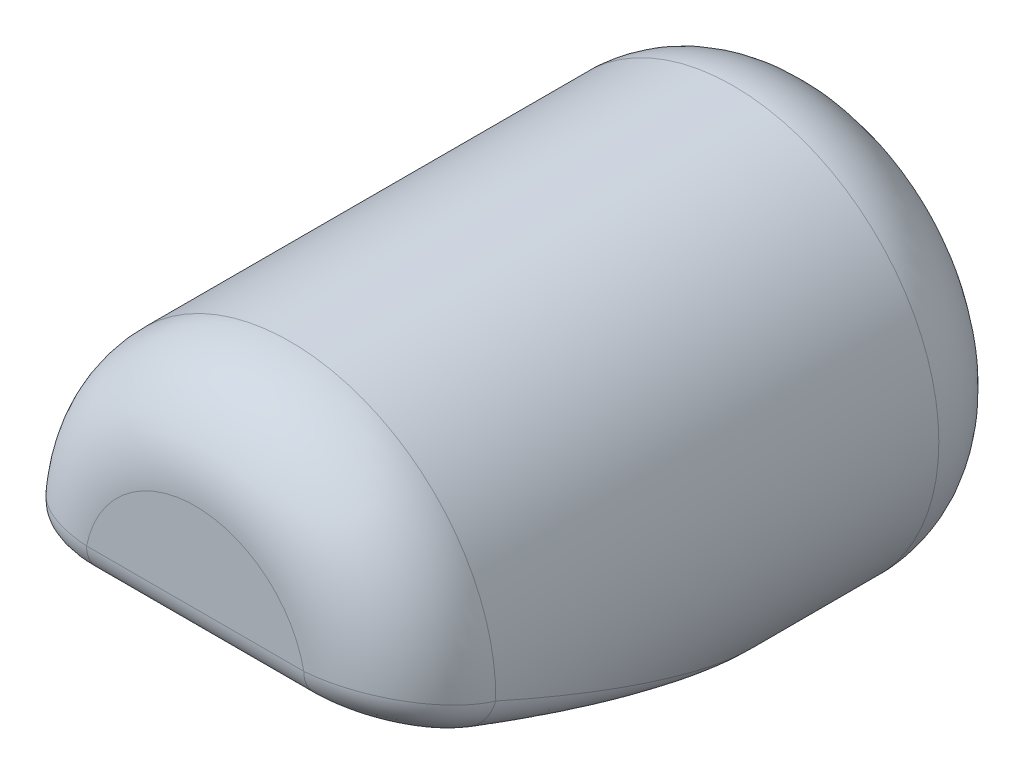
SolidWorks part; units mm, degrees
ref_plane "Front Plane" through (0, 0, 0) normal (0, 0, 1) x (1, 0, 0)
ref_plane "Top Plane" through (0, 0, 0) normal (0, 1, 0) x (1, 0, 0)
ref_plane "Right Plane" through (0, 0, 0) normal (1, 0, 0) x (0, 0, -1)
sketch "Sketch2" plane through (0, 0, 0) normal (0, 0, 1) x (1, 0, 0)
  circle A0 centre (0, 0) radius 6.5
  dimension "D1" = 13
extrude "Boss-Extrude1" add sketch "Sketch2" along normal blind 20
ref_point "Point1"
ref_point "Point2"
fillet "Fillet1" radius 3 2 edges at (6.5, 0, 20) (6.5, 0, 0)
sketch "Sketch3" plane through (0, 0, 0) normal (1, 0, 0) x (0, 0, -1)
  line L0 (-20, 0) -> (-3, -6.5)
  line L1 (-3, -6.5) -> (-3, -10.4048)
  line L2 (-3, -10.4048) -> (-20, -10.4048)
  line L3 (-20, 0) -> (-20, 1000) construction
  line L4 (-20, 50) -> (-20, -50) construction
  line L5 (-20, -10.4048) -> (-20, 0)
extrude "Cut-Extrude1" cut sketch "Sketch3" against normal blind 10 and the other way blind 10
fillet "Fillet2" radius 1 5 edges at (4.171, -4.9853, 6.9616) (5.7884, -0.412, 18.9224) (-4.171, -4.9853, 6.9616) (-5.8431, -0.4386, 18.8528) (0, 0, 20)
